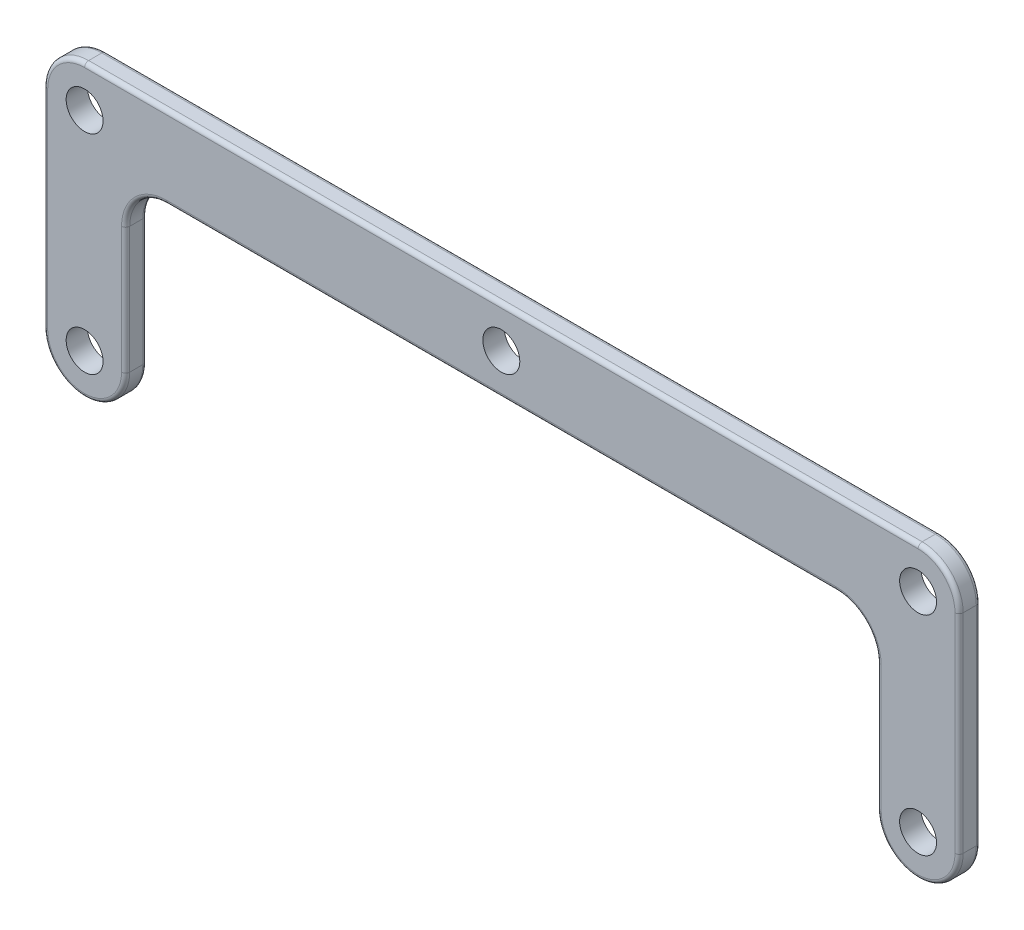
SolidWorks part; units mm, degrees
ref_plane "Front Plane" through (0, 0, 0) normal (0, 0, 1) x (1, 0, 0)
ref_plane "Top Plane" through (0, 0, 0) normal (0, 1, 0) x (1, 0, 0)
ref_plane "Right Plane" through (0, 0, 0) normal (1, 0, 0) x (0, 0, -1)
sketch "Sketch1" plane through (0, 0, 0) normal (0, 0, 1) x (1, 0, 0)
  line L0 (-5, 5) -> (-5, -30.4)
  line L1 (-5, 5) -> (106.6, 5)
  line L5 (-5, -30.4) -> (5, -30.4)
  line L6 (5, -30.4) -> (5, -5)
  line L7 (5, -5) -> (96.6, -5)
  line L8 (96.6, -5) -> (96.6, -30.4)
  line L9 (96.6, -30.4) -> (106.6, -30.4)
  line L10 (106.6, -30.4) -> (106.6, 5)
  circle A0 centre (0, 0) radius 2.25
  circle A1 centre (101.6, 0) radius 2.25
  circle A2 centre (0, -25.4) radius 2.25
  circle A3 centre (101.6, -25.4) radius 2.25
  circle A4 centre (50.8, 0) radius 2.25
  point P20 (50.8, 0)
  dimension "D1" = 4.5
  dimension "D11" = 4.5
  dimension "D2" = 101.6
  dimension "D3" = 5
  dimension "D4" = 5
  dimension "D5" = 5
  dimension "D6" = 10
  dimension "D7" = 10
  dimension "D8" = 10
  dimension "D9" = 25.4
  dimension "D10" = 5
  dimension "D12" = 50.8
extrude "Boss-Extrude1" add sketch "Sketch1" along normal blind 2.6
fillet "Fillet1" radius 5 8 edges at (96.6, -30.4, 1.3) (106.6, -30.4, 1.3) (106.6, 5, 1.3) (96.6, -5, 1.3) (-5, 5, 1.3) (-5, -30.4, 1.3) (5, -30.4, 1.3) (5, -5, 1.3)
fillet "Fillet2" radius 0.5 28 edges at (3.5355, -28.9355, 0) (-3.5355, -28.9355, 0) (-5, -12.7, 0) (-3.5355, 3.5355, 0) (50.8, 5, 0) (105.1355, 3.5355, 0) (106.6, -12.7, 0) (105.1355, -28.9355, 0) (98.0645, -28.9355, 0) (96.6, -17.7, 0) (95.1355, -6.4645, 0) (50.8, -5, 0) (6.4645, -6.4645, 0) (6.4645, -6.4645, 2.6) (5, -17.7, 2.6) (3.5355, -28.9355, 2.6) (-3.5355, -28.9355, 2.6) (-5, -12.7, 2.6) (-3.5355, 3.5355, 2.6) (50.8, 5, 2.6) (105.1355, 3.5355, 2.6) (106.6, -12.7, 2.6) (105.1355, -28.9355, 2.6) (98.0645, -28.9355, 2.6) (96.6, -17.7, 2.6) (95.1355, -6.4645, 2.6) (5, -17.7, 0) (50.8, -5, 2.6)
